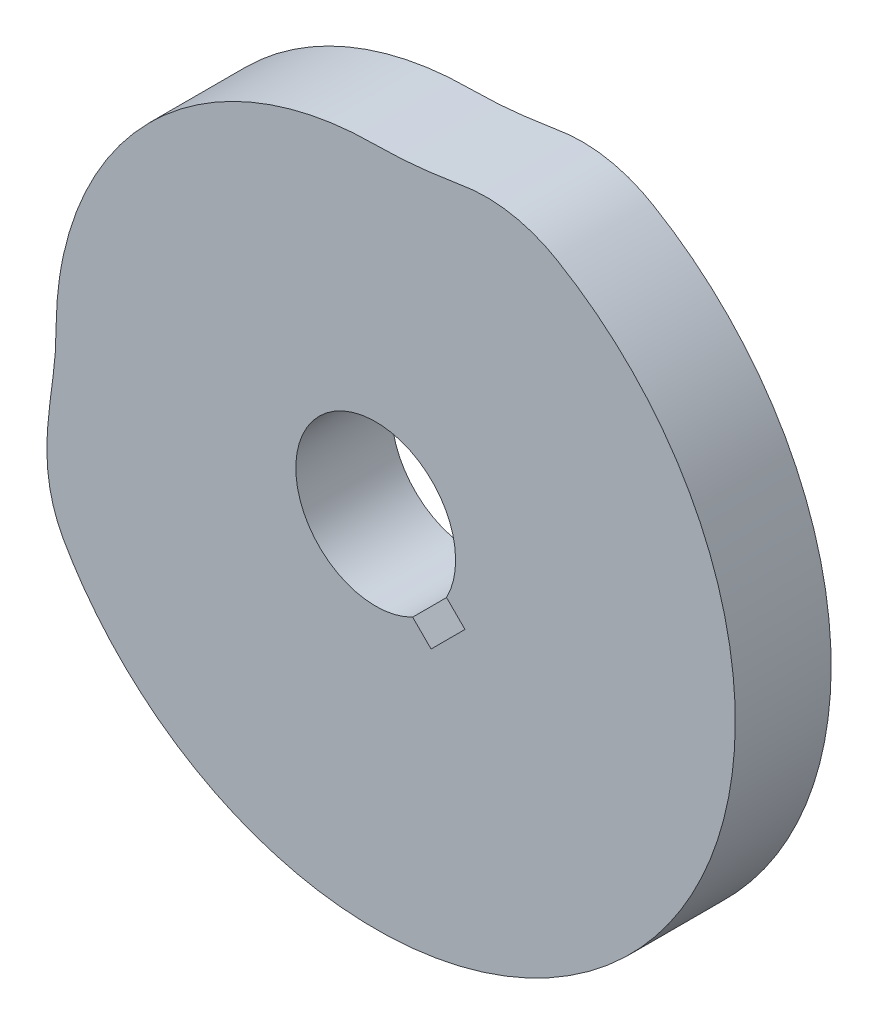
SolidWorks part; units mm, degrees
material "45"
ref_plane "前视基准面" through (0, 0, 0) normal (0, 0, 1) x (1, 0, 0)
ref_plane "上视基准面" through (0, 0, 0) normal (0, 1, 0) x (1, 0, 0)
ref_plane "右视基准面" through (0, 0, 0) normal (1, 0, 0) x (0, 0, -1)
ref_axis "基准轴1" through (0, 0, -88.99) along (0, 0, 1)
sketch "草图1" plane through (0, 0, 0) normal (0, 0, 1) x (1, 0, 0)
  arc A0 (22.5, 38.9711) -> (-38.9711, -22.5) centre (0, 0) cw construction
  arc A1 (-40, 0) -> (0, 40) centre (0, 0) cw construction
  spline S0 degree 3 poles (0, 40) (0.4659, 40) (1.1657, 40.0101) (2.0998, 40.0435) (2.8042, 40.0784) (3.5123, 40.1231) (4.2252, 40.1774) (4.9437, 40.2411) (5.6688, 40.3139) (6.4014, 40.3956) (7.1424, 40.4858) (7.8927, 40.5843) (8.6532, 40.6905) (9.4248, 40.8045) (10.2085, 40.924) (11.0011, 41.0548) (11.8014, 41.1702) (12.6062, 41.2438) (13.4102, 41.282) (14.2121, 41.2832) (15.0105, 41.2482) (15.804, 41.177) (16.5912, 41.07) (17.3708, 40.9276) (18.1415, 40.7501) (18.9018, 40.538) (19.6505, 40.2917) (20.3862, 40.0118) (21.348, 39.5947) (22.0465, 39.233) (22.5, 38.9711) knots 0 0 0 0 0.060822 0.091353 0.122025 0.152885 0.18398 0.215354 0.247051 0.279114 0.311584 0.3445 0.377903 0.41183 0.446315 0.481395 0.516699 0.55185 0.586859 0.621738 0.656498 0.691151 0.725707 0.760179 0.794576 0.82891 0.863191 0.89743 0.931638 1 1 1 1 construction
  spline S1 degree 3 poles (-38.9711, -22.5) (-39.2331, -22.0464) (-39.5903, -21.3449) (-39.9926, -20.376) (-40.2578, -19.6335) (-40.4865, -18.8774) (-40.6794, -18.1097) (-40.8374, -17.3325) (-40.9618, -16.5478) (-41.0541, -15.7575) (-41.1162, -14.9636) (-41.1503, -14.168) (-41.1585, -13.3724) (-41.1435, -12.5784) (-41.1079, -11.7876) (-41.0545, -11.001) (-40.9862, -10.22) (-40.9061, -9.4453) (-40.817, -8.6778) (-40.722, -7.9177) (-40.6239, -7.1656) (-40.5255, -6.4213) (-40.4295, -5.6848) (-40.3385, -4.9557) (-40.2546, -4.2336) (-40.1799, -3.5178) (-40.1163, -2.8074) (-40.0652, -2.1014) (-40.0155, -1.1665) (-39.9999, -0.4661) (-40, 0) knots 0 0 0 0 0.068523 0.102834 0.137201 0.171635 0.206141 0.24072 0.275365 0.310062 0.34479 0.379523 0.414228 0.448869 0.483406 0.517797 0.552 0.585975 0.619685 0.653096 0.686183 0.718927 0.751317 0.783355 0.815051 0.846427 0.877517 0.908364 0.939019 1 1 1 1 construction
  spline S2 degree 3 poles (-39.5852, 5.7455) (-36.9449, 23.9365) (-23.9494, 36.9366) (-5.7593, 39.5832) (-4.493, 39.7674) (-1.9428, 40.0144) (1.9085, 39.9863) (4.4609, 40.186) (5.7333, 40.3221) (5.955, 40.3458) (6.4238, 40.3983) (7.1424, 40.4858) (7.8927, 40.5843) (8.6532, 40.6905) (9.4248, 40.8045) (10.2085, 40.924) (11.0011, 41.0548) (11.8014, 41.1702) (12.6062, 41.2438) (13.4102, 41.282) (14.2121, 41.2832) (15.0105, 41.2482) (15.804, 41.177) (16.5912, 41.07) (17.3708, 40.9276) (18.1415, 40.7501) (18.9018, 40.538) (19.6505, 40.2917) (20.3862, 40.0118) (20.9687, 39.7592) (21.3054, 39.6) (21.4047, 39.5519) (21.5257, 39.4932) (21.7663, 39.373) (22.1243, 39.1863) (22.3579, 39.0531) (22.4744, 38.9859) (22.6003, 38.9133) (22.8515, 38.7669) (23.226, 38.5437) (23.4743, 38.3924) (23.598, 38.3162) (50.6181, 21.6752) (54.174, -9.8584) (31.5383, -32.0988) (8.9027, -54.3392) (-22.5634, -50.2285) (-38.7259, -22.9195) (-38.755, -22.8703) (-38.8131, -22.7717) (-38.8997, -22.6236) (-38.957, -22.5246) (-38.9855, -22.4751) (-39.0101, -22.4324) (-39.0591, -22.3471) (-39.1303, -22.2178) (-39.1773, -22.1313) (-39.2005, -22.0879) (-39.3737, -21.7648) (-39.6506, -21.1997) (-39.9926, -20.376) (-40.2578, -19.6335) (-40.4865, -18.8774) (-40.6794, -18.1097) (-40.8374, -17.3325) (-40.9618, -16.5478) (-41.0541, -15.7575) (-41.1162, -14.9636) (-41.1503, -14.168) (-41.1585, -13.3724) (-41.1435, -12.5784) (-41.1079, -11.7876) (-41.0545, -11.001) (-40.9862, -10.22) (-40.9061, -9.4453) (-40.817, -8.6778) (-40.722, -7.9177) (-40.6239, -7.1656) (-40.5268, -6.4313) (-40.4638, -5.9476) (-40.4337, -5.712) (-40.2718, -4.4458) (-39.982, -1.909) (-40.0143, 1.938) (-39.7686, 4.4822) (-39.5852, 5.7455) (-36.9449, 23.9365) (-23.9494, 36.9366) knots -0.015395 0 0 0 0.192336 0.192336 0.192336 0.207768 0.2232 0.238631 0.238631 0.238631 0.241321 0.24432 0.247361 0.250447 0.253581 0.256767 0.260008 0.263269 0.266516 0.26975 0.272972 0.276183 0.279385 0.282577 0.285762 0.288939 0.292111 0.295278 0.298441 0.301601 0.302932 0.302932 0.302932 0.304553 0.306175 0.307796 0.307796 0.307796 0.309549 0.311302 0.313054 0.313054 0.313054 0.59789 0.59789 0.59789 0.882725 0.882725 0.882725 0.883415 0.884105 0.884794 0.884794 0.884794 0.885388 0.885981 0.886574 0.886574 0.886574 0.890995 0.894158 0.897326 0.9005 0.903681 0.906868 0.910062 0.91326 0.916462 0.919663 0.922862 0.926056 0.929239 0.932409 0.935562 0.938694 0.941802 0.944882 0.947931 0.95095 0.953814 0.953814 0.953814 0.969209 0.984605 1 1 1 1.192336 1.192336 1.192336 weights 1 0.86763 0.86763 1 1 1 1 1 1 1 1 1 1 1 1 1 1 1 1 1 1 1 1 1 1 1 1 1 1 1 1 1 1 1 1 1 1 1 1 1 1 1 0.744339 0.744339 1 0.744339 0.744339 1 1 1 1 1 1 1 1 1 1 1 1 1 1 1 1 1 1 1 1 1 1 1 1 1 1 1 1 1 1 1 1 1 1 1 1 1 1 1 0.86763 0.86763 only from (-39.5852, 5.7455) to (-39.5852, 5.7455)
extrude "凸台-拉伸1" add sketch "草图1" along normal blind 12
sketch "草图2" plane through (0, 0, 0) normal (0, 0, 1) x (1, 0, 0)
  line L0 (8.8667, -4.624) -> (11.1723, -6.9296)
  line L1 (11.1723, -6.9296) -> (6.9296, -11.1723)
  line L2 (6.9296, -11.1723) -> (4.624, -8.8667)
  arc A0 (8.8667, -4.624) -> (4.624, -8.8667) centre (0, 0) ccw
extrude "切除-拉伸1" cut sketch "草图2" against normal blind 12 and the other way blind 12
